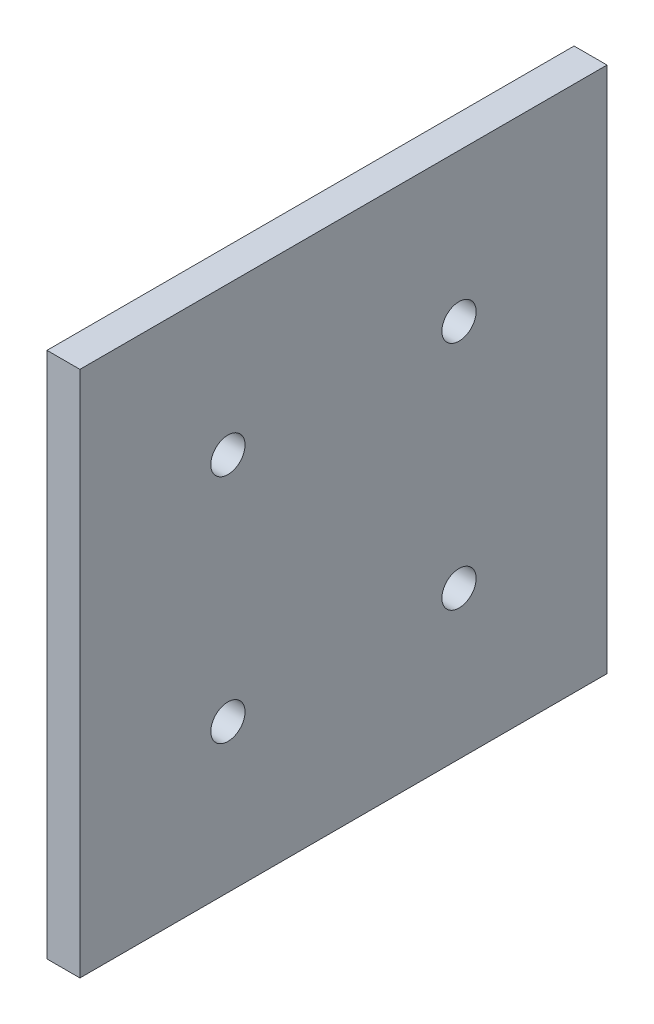
SolidWorks part; units mm, degrees
ref_plane "Front Plane" through (0, 0, 0) normal (0, 0, 1) x (1, 0, 0)
ref_plane "Top Plane" through (0, 0, 0) normal (0, 1, 0) x (1, 0, 0)
ref_plane "Right Plane" through (0, 0, 0) normal (1, 0, 0) x (0, 0, -1)
sketch "Sketch1" plane through (0, 0, 0) normal (1, 0, 0) x (0, 0, -1)
  line L1 (-25.4, -25.4) -> (25.4, -25.4)
  line L2 (-25.4, -25.4) -> (-25.4, 25.4)
  line L3 (-25.4, 25.4) -> (25.4, 25.4)
  line L4 (25.4, -25.4) -> (25.4, 25.4)
  line L5 (-25.4, -25.4) -> (25.4, 25.4) construction
  line L6 (-25.4, 25.4) -> (25.4, -25.4) construction
  point P0 (0, 0)
  dimension "D1" = 50.8
  dimension "D2" = 50.8
extrude "Boss-Extrude1" add sketch "Sketch1" along normal blind 3.175
hole_wizard "M4x0.7 Tapped Hole1" positions "Sketch3" profile "Sketch2" tap size "M4x0.7" standard "ANSI Metric" end condition through all
sketch "Sketch3" plane through (3.175, 0, 0) normal (1, 0, 0) x (0, 0, -1)
  line L1 (-11.1369, -11.1369) -> (11.1369, -11.1369) construction
  line L2 (-11.1369, -11.1369) -> (-11.1369, 11.1369) construction
  line L3 (-11.1369, 11.1369) -> (11.1369, 11.1369) construction
  line L4 (11.1369, -11.1369) -> (11.1369, 11.1369) construction
  line L5 (-11.1369, -11.1369) -> (11.1369, 11.1369) construction
  line L6 (-11.1369, 11.1369) -> (11.1369, -11.1369) construction
  point P219 (11.1369, 11.1369)
  point P223 (-11.1369, 11.1369)
  point P225 (-11.1369, -11.1369)
  point P227 (11.1369, -11.1369)
  dimension "D1" = 31.5
sketch "Sketch2" plane through (3.175, 11.1369, -11.1369) normal (0, 1, 0) x (0, 0, -1)
  line L0 (0, 0) -> (0, 3.175)
  line L1 (0, 3.175) -> (1.65, 3.175)
  line L2 (1.65, 3.175) -> (1.65, 0)
  line L5 (1.65, 0) -> (0, 0)
  line L11 (0, -6.35) -> (0, 107.95) construction
  dimension "Thread Major Dia." = 3.3
  dimension "Thru Tap Drill Depth" = 3.175
